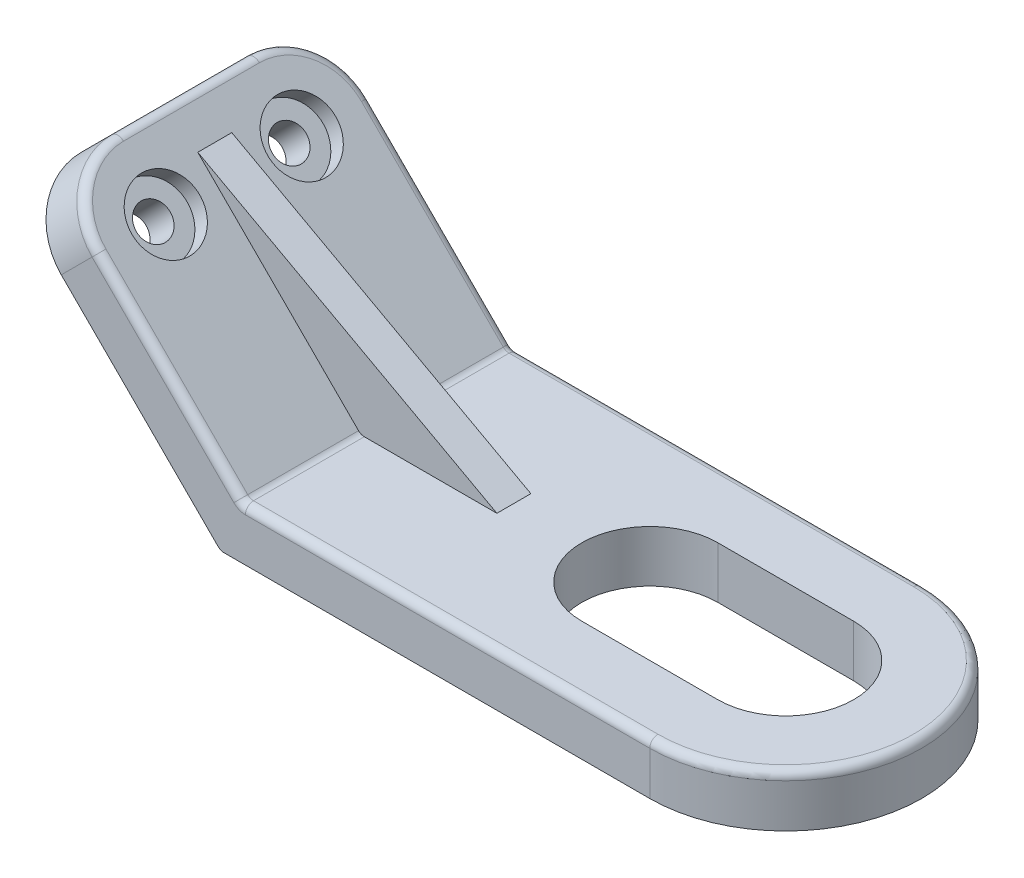
SolidWorks part; units mm, degrees
material "ABS"
ref_plane "Front Plane" through (0, 0, 0) normal (0, 0, 1) x (1, 0, 0)
ref_plane "Top Plane" through (0, 0, 0) normal (0, 1, 0) x (1, 0, 0)
ref_plane "Right Plane" through (0, 0, 0) normal (1, 0, 0) x (0, 0, -1)
sketch "Sketch2" plane through (0, 0, 0) normal (0, 0, 1) x (1, 0, 0)
  line L0 (0, 0) -> (101.6, 0)
  line L1 (0, 0) -> (-35.921, 35.921)
  dimension "D1" = 101.6
  dimension "D2" = 50.8
  dimension "D3" = 45
extrude "Extrude-Thin1" add sketch "Sketch2" along normal mid plane 50.8 thin thin type one direction reverse wall 9.652
sketch "Sketch3" plane through (0, 0, 0) normal (0, 1, 0) x (1, 0, 0)
  line L0 (50.8, 0) -> (76.2, 0) construction
  line L1 (50.8, 12.7) -> (76.2, 12.7)
  line L2 (50.8, -12.7) -> (76.2, -12.7)
  line L3 (101.6, -25.4) -> (101.6, 25.4) construction
  arc A0 (50.8, 12.7) -> (50.8, -12.7) centre (50.8, 0) ccw
  arc A1 (76.2, -12.7) -> (76.2, 12.7) centre (76.2, 0) ccw
  point P3 (63.5, 0)
  dimension "D3" = 25.4
  dimension "D1" = 12.7
  dimension "D2" = 25.4
extrude "Cut-Extrude1" cut sketch "Sketch3" against normal through all
hole_wizard "CBORE for #00 Binding Head Machine Screw1" positions "Sketch4" profile "Sketch5" counterbore size "#00" standard "ANSI Inch" end condition through all
sketch "Sketch4" plane through (0, 0, 0) normal (0.7071, 0.7071, 0) x (0.7071, -0.7071, 0)
  line L0 (-50.8, -25.4) -> (-50.8, 25.4) construction
  line L1 (0, -25.4) -> (-50.8, -25.4) construction
  point P0 (-38.1, -12.7)
  dimension "D1" = 12.7
  dimension "D2" = 12.7
sketch "Sketch5" plane through (-26.9408, 26.9408, 12.7) normal (0, 0, 1) x (-0.7071, 0.7071, 0)
  line L0 (0, 0) -> (0, 37.051)
  line L1 (0, 37.051) -> (3.175, 37.051)
  line L3 (3.175, 37.051) -> (3.175, 3.302)
  line L4 (3.175, 3.302) -> (6.35, 3.302)
  line L5 (6.35, 3.302) -> (6.35, 0)
  line L7 (6.35, 0) -> (0, 0)
  line L11 (0, -6.35) -> (0, 107.95) construction
  dimension "Thru Hole Dia." = 6.35
  dimension "Thru Hole Depth" = 37.051
  dimension "C'Bore Dia." = 12.7
  dimension "C'Bore Depth" = 3.302
mirror "Mirror1" about plane through (0, 0, 0) normal (0, 0, 1) of "CBORE for #00 Binding Head Machine Screw1"
sketch "Sketch6" plane through (0, 0, 0) normal (0, 0, 1) x (1, 0, 0)
  line L0 (-30.48, 30.48) -> (25.4, 0)
  line L1 (0, 0) -> (-35.921, 35.921) construction
  line L2 (101.6, 0) -> (0, 0) construction
  dimension "D1" = 30.48
  dimension "D2" = 25.4
rib "Rib1" sketch "Sketch6" sketch "Sketch6" thickness 6.35 extrusion direction parallel to sketch draft on no parameters "D1"=6.35
fillet "Fillet1" radius 12.7 2 edges at (-39.3335, 32.5085, -25.4) (-39.3335, 32.5085, 25.4)
fillet "Fillet2" radius 1.524 3 edges at (-3.998, -9.652, 0) (0, 0, -14.2875) (0, 0, 14.2875)
fillet "Fillet3" 2 edges at (101.6, -4.826, 25.4) (101.6, -4.826, -25.4) type full round first side face at (16.8473, 2.3474, 25.4) second side face at (16.8473, 2.3474, -25.4) middle face at (101.6, -4.826, 0)
fillet "Fillet4" radius 1.524 10 edges at (0.0481, 0.116, 25.4) (38.4156, 0, 25.4) (101.6, 0, 0) (38.4156, 0, -25.4) (0.0481, 0.116, -25.4) (-13.6936, 13.6936, -25.4) (-33.2908, 33.2908, -21.6803) (-35.921, 35.921, 0) (-33.2908, 33.2908, 21.6803) (-13.6936, 13.6936, 25.4)
